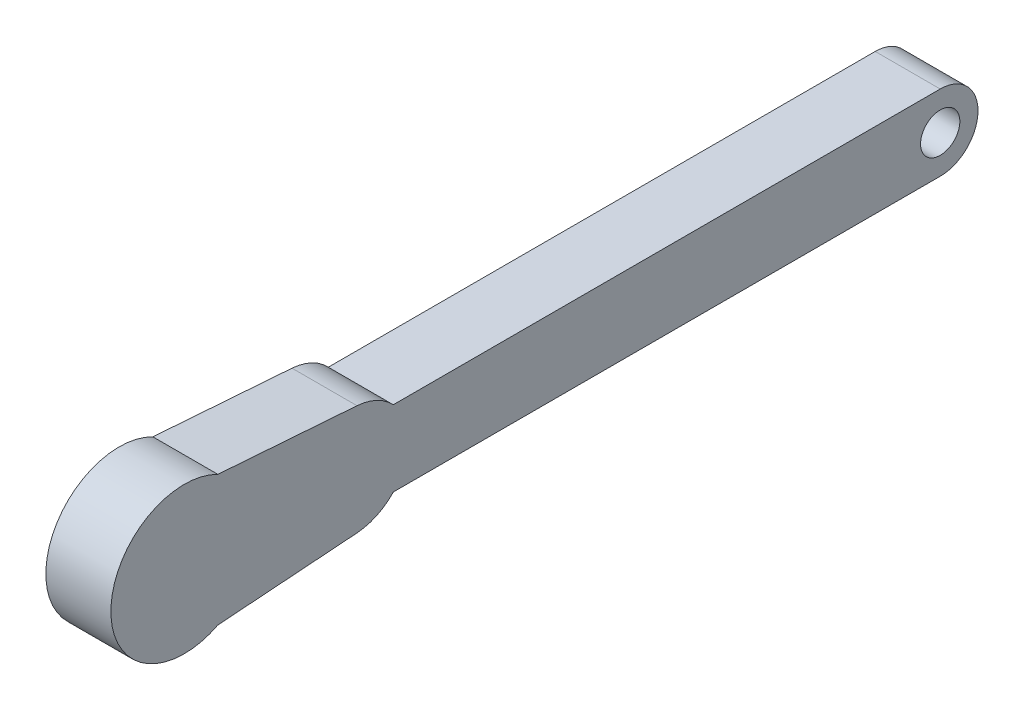
SolidWorks part; units mm, degrees
note: '?' marks a value the reader was unsure of.
material "ABS"
ref_plane "Front Plane" through (0, 0, 0) normal (0, 0, 1) x (1, 0, 0)
ref_plane "ARM PLANE" through (0, 0, 0) normal (0, 1, 0) x (1, 0, 0)
ref_plane "Right Plane" through (0, 0, 0) normal (1, 0, 0) x (0, 0, -1)
other "Configuration Table"
sketch "Sketch2" plane through (0, 0, 0) normal (0, 1, 0) x (1, 0, 0)
  line L0 (2.7305, -23.1775) -> (-2.7305, -23.1775)
  line L2 (-2.7305, -23.1775) -> (-2.7305, 48.5775)
  line L4 (2.7305, -23.1775) -> (2.7305, 48.5775)
  line L17 (-2.7305, 48.5775) -> (2.7305, 48.5775)
  line L18 (-2.7305, -18.0975) -> (2.7305, -18.0975) construction
  line L19 (-2.7305, 45.4025) -> (2.7305, 45.4025) construction
  point P0 (0, 0)
  point P13 (0, -18.0975)
  dimension "D2" = 5.461
  dimension "D6" = 5.08
  dimension "D1" = 63.5
  dimension "D3" = 3.175
  dimension "D4" = 18.0975
extrude "Boss-Extrude1" add sketch "Sketch2" along normal mid plane 6.35
ref_axis "Axis1" through (-2.7305, 0, 18.0975) along (1, 0, 0)?
sketch "Sketch7" plane through (-2.7305, 0, 0) normal (-1, 0, 0) x (0, -1, 0)
  line L0 (-2.0944, 3.7697) -> (-2.99, 16.048) construction
  line L1 (2.99, 16.048) -> (2.0944, 3.7697) construction
  line L2 (2.99, 16.048) -> (2.0944, 3.7697) construction
  line L3 (-2.0944, 3.7697) -> (-2.99, 16.048) construction
  line L4 (5.4803, 15.2737) -> (4.6277, 3.585)
  line L5 (-4.6277, 3.585) -> (-5.4803, 15.2737)
  arc A0 (-2.0944, 3.7697) -> (2.0944, 3.7697) centre (0, 3.9225) ccw construction
  circle A1 centre (0, 18.0975) radius 3.625 construction
  arc A2 (2.99, 16.048) -> (-2.99, 16.048) centre (0, 18.0975) ccw construction
  arc A3 (-2.0944, 3.7697) -> (2.0944, 3.7697) centre (0, 3.9225) ccw construction
  arc A4 (-4.6277, 3.585) -> (4.6277, 3.585) centre (0, 3.9225) ccw
  arc A5 (5.4803, 15.2737) -> (-5.4803, 15.2737) centre (0, 18.0975) ccw
  dimension "D1" = 2.54
extrude "Boss-Extrude2" add sketch "Sketch7" against normal up to surface (5.461 mm away) up to face at (2.7305, 0, -12.7)
sketch "Sketch10" plane through (-2.7305, 0, 0) normal (-1, 0, 0) x (0, -1, 0)
  line L0 (-3.1142, 16.0048) -> (-2.2211, 3.7605)
  line L1 (2.2211, 3.7605) -> (3.1142, 16.0048)
  line L2 (2.0944, 3.7697) -> (2.99, 16.048)
  line L3 (-2.99, 16.048) -> (-2.0944, 3.7697)
  line L4 (2.0944, 3.7697) -> (2.99, 16.048) construction
  line L5 (-2.99, 16.048) -> (-2.0944, 3.7697) construction
  arc A0 (3.1142, 16.0048) -> (-3.1142, 16.0048) centre (0, 18.0975) ccw
  arc A1 (-2.2211, 3.7605) -> (2.2211, 3.7605) centre (0, 3.9225) ccw
  arc A2 (2.99, 16.048) -> (-2.99, 16.048) centre (0, 18.0975) ccw
  arc A3 (-2.0944, 3.7697) -> (2.0944, 3.7697) centre (0, 3.9225) ccw
  arc A4 (2.99, 16.048) -> (-2.99, 16.048) centre (0, 18.0975) ccw construction
  arc A5 (-2.0944, 3.7697) -> (2.0944, 3.7697) centre (0, 3.9225) ccw construction
  dimension "D1" = 0
  dimension "D2" = 0.127
extrude "Cut-Extrude1" cut sketch "Sketch10" against normal blind 2.032
hole_wizard "M3 Clearance Hole clearence" positions "Sketch15" profile "Sketch16" hole size "M3" standard "ANSI Metric" end condition through all
sketch "Sketch15" plane through (-2.7305, 0, 0) normal (-1, 0, 0) x (0, 0, 1)
  point P2 (-45.4025, 0)
sketch "Sketch16" plane through (-2.7305, 0, -45.4025) normal (0, 1, 0) x (0, 0, 1)
  line L0 (0, 0) -> (0, 5.461)
  line L1 (0, 5.461) -> (1.65, 5.461)
  line L2 (1.65, 5.461) -> (1.65, 0)
  line L5 (1.65, 0) -> (0, 0)
  line L11 (0, -6.35) -> (0, 107.95) construction
  dimension "Thru Hole Dia." = 3.3
  dimension "Thru Hole Depth" = 5.461
fillet "Fillet1" radius 3.175 2 edges at (0, -3.175, -48.5775) (0, 3.175, -48.5775)
sketch "Sketch19" plane through (-0.6985, 0, 0) normal (-1, 0, 0) x (0, 0, 1)
  circle A0 centre (18.0975, 0) radius 2
  dimension "D1" = 4
extrude "Cut-Extrude2" cut sketch "Sketch19" against normal blind 0.5
chamfer "Chamfer1" distance 0.5 angle 45 1 edges at (-0.6985, 0, 20.0975)
hole_wizard "Ø2.0mm Dowel Hole1" [suppressed] positions "Sketch22" profile "Sketch23" hole size "Ø2.0" standard "ANSI Metric"
sketch "Sketch22" plane through (-0.6985, 0, 0) normal (-1, 0, 0) x (0, 0, 1)
  point P0 (3.4225, 0)
sketch "Sketch23" plane through (-0.6985, 0, 3.4225) normal (0, 1, 0) x (0, 0, 1)
  line L0 (0, 0) -> (0, 3.429)
  line L1 (0, 3.429) -> (1, 3.429)
  line L2 (1, 3.429) -> (1, 0)
  line L5 (1, 0) -> (0, 0)
  line L11 (0, -6.35) -> (0, 107.95) construction
  dimension "Thru Hole Dia." = 2
  dimension "Thru Hole Depth" = 3.429
equation "\"arm_length\"= 2.5"
equation "\"D1@Sketch2\"=\"arm_length\""
